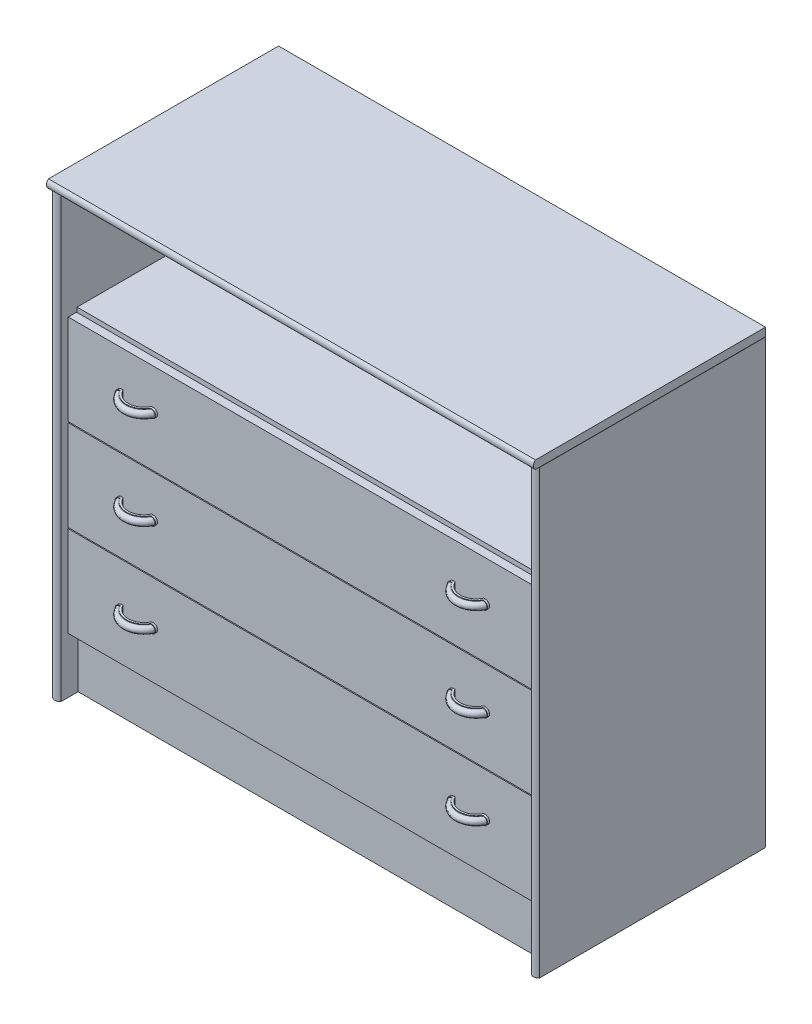
SolidWorks part; units mm, degrees
material "Hêtre"
ref_plane "Plan de face" through (0, 0, 0) normal (0, 0, 1) x (1, 0, 0)
ref_plane "Plan de dessus" through (0, 0, 0) normal (0, 1, 0) x (1, 0, 0)
ref_plane "Plan de droite" through (0, 0, 0) normal (1, 0, 0) x (0, 0, -1)
sketch "Esquisse1" plane through (0, 0, 0) normal (0, 1, 0) x (1, 0, 0)
  line L0 (-470, -218) -> (-470, 218)
  line L1 (-470, 218) -> (470, 218)
  line L2 (470, 218) -> (470, -218)
  line L3 (-470, 0) -> (470, 0) construction
  line L4 (-454, -218) -> (-454, -212)
  line L5 (-454, -218) -> (-470, -218) construction
  line L6 (470, -218) -> (454, -218) construction
  line L7 (-462, -222) -> (462, -222) construction
  line L8 (-454, -212) -> (454, -212)
  line L9 (454, -212) -> (454, -218)
  arc A0 (454, -218) -> (470, -218) centre (462, -212) ccw
  arc A1 (-470, -218) -> (-454, -218) centre (-462, -212) ccw
  point P9 (-462, -218)
  point P10 (462, -218)
  dimension "D4" = 16
  dimension "D1" = 940
  dimension "D2" = 4
  dimension "D3" = 440
  dimension "D5" = 6
extrude "Boss.-Extru.1" add sketch "Esquisse1" along normal blind 870
sketch "Esquisse2" plane through (470, 0, 0) normal (1, 0, 0) x (0, 0, -1)
  line L0 (-196, 870) -> (-226, 870)
  line L1 (-226, 870) -> (-226, 854) construction
  line L2 (-226, 854) -> (-196, 854)
  line L4 (-218, 870) -> (218, 870) construction
  line L5 (218, 870) -> (218, 0) construction
  line L6 (-196, 870) -> (-196, 854)
  arc A0 (-226, 870) -> (-226, 854) centre (-220, 862) ccw
  point P8 (-230, 862)
  dimension "D1" = 16
  dimension "D2" = 4
  dimension "D3" = 448
  dimension "D4" = 30
extrude "Boss.-Extru.2" add sketch "Esquisse2" against normal through all
sketch "Esquisse4" plane through (-454, 0, 0) normal (1, 0, 0) x (0, 0, -1)
  line L0 (-218, 854) -> (202, 854)
  line L1 (202, 854) -> (202, 644)
  line L2 (202, 644) -> (-187, 644)
  line L3 (-187, 644) -> (-187, 636)
  line L4 (-222, 854) -> (-222, 0) construction
  line L5 (-204, 461) -> (-187, 461)
  line L7 (218, 870) -> (218, 0) construction
  line L8 (-204, 636) -> (-188, 636)
  line L9 (-204, 636) -> (-204, 461)
  line L10 (-187, 461) -> (-187, 459)
  line L11 (-187, 459) -> (-204, 459)
  line L12 (-204, 459) -> (-204, 284)
  line L13 (-204, 284) -> (-187, 284)
  line L14 (-187, 284) -> (-187, 282)
  line L15 (-187, 282) -> (-204, 282)
  line L16 (-204, 282) -> (-204, 107)
  line L17 (-204, 107) -> (-185, 107)
  line L18 (-185, 107) -> (-185, 0)
  line L19 (218, 0) -> (-218, 0) construction
  line L20 (-188, 636) -> (-188, 634)
  line L21 (-188, 634) -> (-187, 634)
  line L22 (-187, 634) -> (-187, 636)
  line L24 (-222, 0) -> (-218, 0) construction
  line L25 (-218, 854) -> (-218, 0)
  line L26 (-218, 0) -> (-185, 0)
  point P30 (-220, 0)
  dimension "D1" = 16
  dimension "D2" = 210
  dimension "D3" = 35
  dimension "D4" = 8
  dimension "D5" = 16
  dimension "D6" = 175
  dimension "D7" = 2
  dimension "D8" = 2
  dimension "D9" = 1
  dimension "D10" = 35
extrude "Enlèv. mat.-Extru.1" cut sketch "Esquisse4" along normal up to surface (908 mm away) up to face at (454, 427, 215)
sketch "Esquisse5" plane through (0, 0, 0) normal (0, 0, 1) x (1, 0, 0)
  line L0 (-470, 854) -> (-462, 854)
  line L1 (-470, 854) -> (-454, 854) construction
  line L2 (-462, 854) -> (-462, 853.5)
  line L3 (-462, 853.5) -> (-470, 853.5)
  line L4 (-470, 854) -> (-470, 0) construction
  line L5 (-470, 853.5) -> (-470, 854)
  line L6 (454, 854) -> (470, 854) construction
  line L7 (470, 854) -> (462, 854)
  line L8 (470, 854) -> (470, 853.5)
  line L9 (470, 853.5) -> (462, 853.5)
  line L10 (462, 854) -> (462, 853.5)
  dimension "D1" = 0.5
  dimension "D2" = 0.5
extrude "Enlèv. mat.-Extru.2" cut sketch "Esquisse5" against normal through all and the other way through all
sketch "Esquisse6" plane through (0, 0, 204) normal (0, 0, 1) x (1, 0, 0)
  line L0 (-348, 567) -> (-348, 551)
  line L1 (-348, 551) -> (-353, 551)
  line L2 (-353, 551) -> (-353, 567) construction
  line L3 (-353, 567) -> (-348, 567)
  line L4 (-454, 854) -> (-454, 0) construction
  line L5 (454, 636) -> (-454, 636) construction
  arc A0 (-353, 567) -> (-353, 551) centre (-353, 559) ccw
  point P5 (-361, 559)
  dimension "D1" = 16
  dimension "D2" = 13
  dimension "D3" = 93
  dimension "D4" = 69
sketch3d "Esquisse3D1"
  line L0 (-320.5, 559, 204) -> (-348, 559, 204) construction
  line L1 (-320.5, 559, 204) -> (-320.5, 559, 221.5) construction
  line L2 (-348, 567, 204) -> (-348, 551, 204) construction
  line L3 (-320.5, 559, 204) -> (-293, 559, 204) construction
  line L4 (-320.5, 559, 204) -> (-320.5, 559, 189) construction
  line L5 (-320.5, 559, 189) -> (-290.2186, 559, 189) construction
  arc A0 (-348, 559, 204) -> (-293, 559, 204) centre (-320.5, 559, 191.1429) cw
  arc A1 (-293, 559, 204) -> (-290.2186, 559, 189) centre (-320.5, 559, 191.1429) cw
  point P7 (-320.5, 589.3571, 191.1429)
  point P11 (-320.5, 589.3571, 191.1429)
  dimension "D1" = 55
  dimension "D2" = 17.5
  dimension "D3" = 15
sweep "Balayage5" add profiles "Esquisse6" path "Esquisse3D1"
sketch "Esquisse8" plane through (0, 0, 204) normal (0, 0, 1) x (1, 0, 0)
  line L2 (-353, 567) -> (-352, 567)
  line L3 (-352, 551) -> (-352, 567)
  line L4 (-352, 551) -> (-352, 552)
  line L5 (-353, 551) -> (-352, 551)
  line L6 (-353, 566) -> (-352, 566)
  line L7 (-353, 552) -> (-352, 552)
  line L8 (-352, 566) -> (-352, 567)
  line L9 (-352, 566) -> (-352, 552) construction
  arc A0 (-353, 567) -> (-353, 551) centre (-353, 559) ccw
  arc A1 (-353, 567) -> (-353, 551) centre (-353, 559) ccw construction
  arc A2 (-353, 566) -> (-353, 552) centre (-353, 559) ccw
  dimension "D1" = 4
  dimension "D2" = 1
sweep "Enlèvement de matière-Balayage1" cut profiles "Esquisse8" path "Esquisse3D1<3>"
sketch3d "Esquisse3D1<3>" same geometry as "Esquisse3D1"
sketch "Esquisse10" plane through (0, 567, 0) normal (0, 1, 0) x (1, 0, 0)
  line L0 (-360, -204) -> (-348, -204)
  line L1 (-348, -204) -> (-348, -208)
  line L2 (-348, -208) -> (-358.4657, -208)
  line L3 (-320.5, -191.1429) -> (-320.5, -232.6827) construction
  line L4 (-293, -208) -> (-282.5343, -208)
  line L5 (-293, -204) -> (-293, -208)
  line L6 (-281, -204) -> (-293, -204) construction
  line L7 (-281, -204) -> (-280, -204) construction
  line L8 (-280, -204) -> (-275.4021, -193.1036)
  line L9 (-275.4021, -193.1036) -> (-287.1717, -189.1804)
  line L10 (-287.1717, -189.1804) -> (-293, -204)
  line L11 (-358.4657, -208) -> (-359.5573, -208)
  line L12 (454, -204) -> (-454, -204) construction
  line L13 (-361.0503, -204) -> (-360, -204)
  line L14 (-282.5343, -208) -> (-281.4427, -208)
  arc A0 (-360, -204) -> (-358.4657, -208) centre (-320.5, -191.1429) ccw construction
  arc A1 (-360, -204) -> (-279.0164, -193.3023) centre (-320.5, -191.1429) ccw construction
  arc A2 (-280.0491, -204.3095) -> (-281.6204, -208.4058) centre (-320.5, -191.1429) cw construction
  arc A16 (-360, -204) -> (-279.0164, -193.3023) centre (-320.5, -191.1429) ccw construction
  arc A32 (-360, -204) -> (-279.0164, -193.3023) centre (-320.5, -191.1429) ccw construction
  arc A39 (-281, -204) -> (-282.5343, -208) centre (-320.5, -191.1429) cw construction
  arc A40 (-279.9497, -204) -> (-281.4427, -208) centre (-320.5, -191.1429) cw
  arc A41 (-361.0503, -204) -> (-359.5573, -208) centre (-320.5, -191.1429) ccw
  arc A42 (-360.9509, -204.3095) -> (-359.3796, -208.4058) centre (-320.5, -191.1429) ccw construction
  arc M1 (-352, -204) -> (-289, -204) centre (-320.5, -191.1429) ccw
  line M4 (-348, -204) -> (-352, -204)
  dimension "D1" = 4
  dimension "D2" = 1
  dimension "D3" = 1
extrude "Boss.-Extru.15" add sketch "Esquisse10" against normal up to surface (16 mm away) contours L13 A41 L11 L2 L0 M1 | L2 L1 M4 M1 region at (-355.7043, 567, 206.0163) region at (-349.5915, 567, 205.7896)
sketch "Esquisse13" plane through (0, 567, 0) normal (0, 1, 0) x (1, 0, 0)
  line L0 (-350.0532, -208) -> (-290.9468, -208) construction
  line L1 (-290.9468, -208) -> (-281.495, -208)
  line L2 (-278.0828, -193.6609) -> (-286.4845, -190.4341)
  line L3 (-286.4845, -190.4341) -> (-290.9468, -208)
  arc A1 (-350.0532, -208) -> (-289, -204) centre (-320.5, -191.1429) ccw construction
  arc A2 (-278.0828, -193.6609) -> (-281.495, -208) centre (-320.5, -191.1429) cw
  arc A16 (-280, -204) -> (-278.0828, -193.6609) centre (-320.5, -191.1429) ccw construction
extrude "Boss.-Extru.16" add sketch "Esquisse13" against normal up to surface (16 mm away)
sketch "Esquisse14" plane through (0, 0, 204) normal (0, 0, 1) x (1, 0, 0)
  line L3 (-289.8831, 567) -> (-280, 567)
  line L4 (-280, 567) -> (-280, 551)
  line L5 (-280, 551) -> (-289.8831, 551)
  line L6 (-351.1169, 567) -> (-361.0503, 567)
  line L7 (-361.0503, 567) -> (-361.0503, 551)
  line L8 (-361.0503, 551) -> (-351.1169, 551)
  spline S6 degree 3 poles (1187.9818, -2008.6458) (-486.8568, 64.8661) (-343.1062, 576.8392) (-288.0439, 566.8105) (-287.7864, 566.7515) (-287.2738, 566.6088) (-287.0184, 566.5248) (-286.2703, 566.239) (-285.7942, 566.0039) (-285.1169, 565.5853) (-284.8974, 565.4347) (-284.4695, 565.1093) (-284.2621, 564.9348) (-283.87, 564.5703) (-283.6835, 564.379) (-283.3304, 563.9788) (-283.1646, 563.7709) (-282.851, 563.3342) (-282.7049, 563.1069) (-282.4362, 562.6386) (-282.3131, 562.3964) (-281.9867, 561.6613) (-281.8198, 561.1515) (-281.6492, 560.3551) (-281.6062, 560.0856) (-281.5491, 559.549) (-281.5347, 559.2803) (-281.5339, 558.7432) (-281.5474, 558.4749) (-281.6031, 557.9362) (-281.6455, 557.666) (-281.813, 556.8725) (-281.9782, 556.3614) (-282.4131, 555.375) (-282.6848, 554.8996) (-283.3069, 554.0286) (-283.6609, 553.6253) (-284.4508, 552.8886) (-284.8768, 552.5644) (-285.5549, 552.1434) (-285.7875, 552.0139) (-286.2677, 551.7759) (-286.5146, 551.6679) (-287.2604, 551.3824) (-287.7702, 551.2401) (-322.3753, 544.8907) (-407.055, 740.1458) (2556.1497, 1476.8068) knots -6.535728 -6.535728 -6.535728 -6.535728 0.0625 0.0625 0.09375 0.09375 0.125 0.125 0.1875 0.1875 0.21875 0.21875 0.25 0.25 0.28125 0.28125 0.3125 0.3125 0.34375 0.34375 0.375 0.375 0.4375 0.4375 0.46875 0.46875 0.5 0.5 0.53125 0.53125 0.5625 0.5625 0.625 0.625 0.6875 0.6875 0.75 0.75 0.8125 0.8125 0.84375 0.84375 0.875 0.875 0.9375 0.9375 5.017384 5.017384 5.017384 5.017384 only from (-289.8831, 567) to (-289.8831, 551)
  spline S7 degree 3 poles (-289.8831, 567) (-289.3497, 567) (-288.8226, 566.9523) (-288.0439, 566.8105) (-287.7864, 566.7515) (-287.2738, 566.6088) (-287.0184, 566.5248) (-286.2703, 566.239) (-285.7942, 566.0039) (-285.1169, 565.5853) (-284.8974, 565.4347) (-284.4695, 565.1093) (-284.2621, 564.9348) (-283.87, 564.5703) (-283.6835, 564.379) (-283.3304, 563.9788) (-283.1646, 563.7709) (-282.851, 563.3342) (-282.7049, 563.1069) (-282.4362, 562.6386) (-282.3131, 562.3964) (-281.9867, 561.6613) (-281.8198, 561.1515) (-281.6492, 560.3551) (-281.6062, 560.0856) (-281.5491, 559.549) (-281.5347, 559.2803) (-281.5339, 558.7432) (-281.5474, 558.4749) (-281.6031, 557.9362) (-281.6455, 557.666) (-281.813, 556.8725) (-281.9782, 556.3614) (-282.4131, 555.375) (-282.6848, 554.8996) (-283.3069, 554.0286) (-283.6609, 553.6253) (-284.4508, 552.8886) (-284.8768, 552.5644) (-285.5549, 552.1434) (-285.7875, 552.0139) (-286.2677, 551.7759) (-286.5146, 551.6679) (-287.2604, 551.3824) (-287.7702, 551.2401) (-288.8144, 551.0485) (-289.3484, 551) (-289.8831, 551) knots 0 0 0 0 0.0625 0.0625 0.09375 0.09375 0.125 0.125 0.1875 0.1875 0.21875 0.21875 0.25 0.25 0.28125 0.28125 0.3125 0.3125 0.34375 0.34375 0.375 0.375 0.4375 0.4375 0.46875 0.46875 0.5 0.5 0.53125 0.53125 0.5625 0.5625 0.625 0.625 0.6875 0.6875 0.75 0.75 0.8125 0.8125 0.84375 0.84375 0.875 0.875 0.9375 0.9375 1 1 1 1
  spline S9 degree 3 poles (-1828.9818, -2008.6458) (-154.1432, 64.8661) (-297.8938, 576.8392) (-352.9561, 566.8105) (-353.2136, 566.7515) (-353.7262, 566.6088) (-353.9816, 566.5248) (-354.7297, 566.239) (-355.2058, 566.0039) (-355.8831, 565.5853) (-356.1026, 565.4347) (-356.5305, 565.1093) (-356.7379, 564.9348) (-357.13, 564.5703) (-357.3165, 564.379) (-357.6696, 563.9788) (-357.8354, 563.7709) (-358.149, 563.3342) (-358.2951, 563.1069) (-358.5638, 562.6386) (-358.6869, 562.3964) (-359.0133, 561.6613) (-359.1802, 561.1515) (-359.3508, 560.3551) (-359.3938, 560.0856) (-359.4509, 559.549) (-359.4653, 559.2803) (-359.4661, 558.7432) (-359.4526, 558.4749) (-359.3969, 557.9362) (-359.3545, 557.666) (-359.187, 556.8725) (-359.0218, 556.3614) (-358.5869, 555.375) (-358.3152, 554.8996) (-357.6931, 554.0286) (-357.3391, 553.6253) (-356.5492, 552.8886) (-356.1232, 552.5644) (-355.4451, 552.1434) (-355.2125, 552.0139) (-354.7323, 551.7759) (-354.4854, 551.6679) (-353.7396, 551.3824) (-353.2298, 551.2401) (-318.6247, 544.8907) (-233.945, 740.1458) (-3197.1497, 1476.8068) knots -6.535728 -6.535728 -6.535728 -6.535728 0.0625 0.0625 0.09375 0.09375 0.125 0.125 0.1875 0.1875 0.21875 0.21875 0.25 0.25 0.28125 0.28125 0.3125 0.3125 0.34375 0.34375 0.375 0.375 0.4375 0.4375 0.46875 0.46875 0.5 0.5 0.53125 0.53125 0.5625 0.5625 0.625 0.625 0.6875 0.6875 0.75 0.75 0.8125 0.8125 0.84375 0.84375 0.875 0.875 0.9375 0.9375 5.017384 5.017384 5.017384 5.017384 only from (-351.1169, 567) to (-351.1169, 551)
  spline S10 degree 3 poles (-351.1169, 567) (-351.6503, 567) (-352.1774, 566.9523) (-352.9561, 566.8105) (-353.2136, 566.7515) (-353.7262, 566.6088) (-353.9816, 566.5248) (-354.7297, 566.239) (-355.2058, 566.0039) (-355.8831, 565.5853) (-356.1026, 565.4347) (-356.5305, 565.1093) (-356.7379, 564.9348) (-357.13, 564.5703) (-357.3165, 564.379) (-357.6696, 563.9788) (-357.8354, 563.7709) (-358.149, 563.3342) (-358.2951, 563.1069) (-358.5638, 562.6386) (-358.6869, 562.3964) (-359.0133, 561.6613) (-359.1802, 561.1515) (-359.3508, 560.3551) (-359.3938, 560.0856) (-359.4509, 559.549) (-359.4653, 559.2803) (-359.4661, 558.7432) (-359.4526, 558.4749) (-359.3969, 557.9362) (-359.3545, 557.666) (-359.187, 556.8725) (-359.0218, 556.3614) (-358.5869, 555.375) (-358.3152, 554.8996) (-357.6931, 554.0286) (-357.3391, 553.6253) (-356.5492, 552.8886) (-356.1232, 552.5644) (-355.4451, 552.1434) (-355.2125, 552.0139) (-354.7323, 551.7759) (-354.4854, 551.6679) (-353.7396, 551.3824) (-353.2298, 551.2401) (-352.1856, 551.0485) (-351.6516, 551) (-351.1169, 551) knots 0 0 0 0 0.0625 0.0625 0.09375 0.09375 0.125 0.125 0.1875 0.1875 0.21875 0.21875 0.25 0.25 0.28125 0.28125 0.3125 0.3125 0.34375 0.34375 0.375 0.375 0.4375 0.4375 0.46875 0.46875 0.5 0.5 0.53125 0.53125 0.5625 0.5625 0.625 0.625 0.6875 0.6875 0.75 0.75 0.8125 0.8125 0.84375 0.84375 0.875 0.875 0.9375 0.9375 1 1 1 1
  dimension "D1" = 1
  dimension "D2" = 1
extrude "Enlèv. mat.-Extru.3" cut sketch "Esquisse14" along normal through all
pattern_linear "Répétition linéaire2" count 3 spacing 180 along (0, -1, 0) count 2 spacing 641 along (1, 0, 0) of "Balayage5", "Enlèvement de matière-Balayage1", "Boss.-Extru.15", "Boss.-Extru.16", "Enlèv. mat.-Extru.3"
